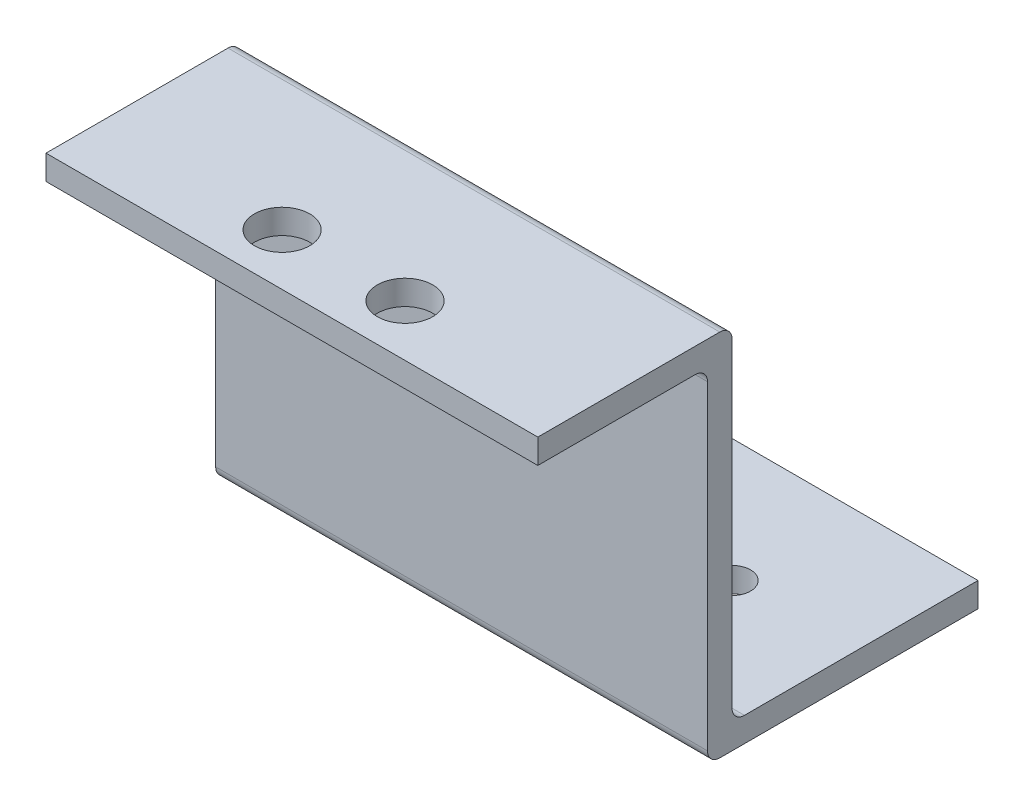
SolidWorks part; units mm, degrees
ref_plane "Front Plane" through (0, 0, 0) normal (0, 0, 1) x (1, 0, 0)
ref_plane "Top Plane" through (0, 0, 0) normal (0, 1, 0) x (1, 0, 0)
ref_plane "Right Plane" through (0, 0, 0) normal (1, 0, 0) x (0, 0, -1)
sketch "Sketch1" plane through (0, 0, 0) normal (0, 1, 0) x (1, 0, 0)
  line L0 (0.736, 26.632) -> (1.236, 26.632)
  line L1 (0.736, 26.632) -> (0.736, 19.832)
  line L2 (0.736, 19.832) -> (1.236, 19.832)
  line L3 (1.236, 26.632) -> (1.236, 19.832)
  line L4 (0.736, 26.632) -> (0.236, 26.632)
  line L5 (0.736, 26.632) -> (0.736, 19.832)
  line L6 (0.736, 19.832) -> (0.236, 19.832)
  line L7 (0.236, 26.632) -> (0.236, 19.832)
  line L8 (0.736, 19.832) -> (10.736, 19.832)
  line L9 (0.736, 19.832) -> (0.736, -20.568)
  line L10 (0.736, -20.568) -> (10.736, -20.568)
  line L11 (10.736, 19.832) -> (10.736, -20.568)
  line L12 (0.736, 19.832) -> (-9.264, 19.832)
  line L13 (0.736, 19.832) -> (0.736, -20.568)
  line L14 (0.736, -20.568) -> (-9.264, -20.568)
  line L15 (-9.264, 19.832) -> (-9.264, -20.568)
  line L16 (0.736, -20.568) -> (1.236, -20.568)
  line L17 (0.736, -20.568) -> (0.736, -27.368)
  line L18 (0.736, -27.368) -> (1.236, -27.368)
  line L19 (1.236, -20.568) -> (1.236, -27.368)
  line L20 (0.736, -20.568) -> (0.236, -20.568)
  line L21 (0.736, -20.568) -> (0.736, -27.368)
  line L22 (0.736, -27.368) -> (0.236, -27.368)
  line L23 (0.236, -20.568) -> (0.236, -27.368)
  line L25 (-19.264, 49.632) -> (20.736, 49.632)
  line L26 (-19.264, 49.632) -> (-19.264, -50.368)
  line L27 (-19.264, -50.368) -> (20.736, -50.368)
  line L28 (20.736, 49.632) -> (20.736, -50.368)
  circle A0 centre (-4.264, 24.032) radius 2.25
  circle A1 centre (5.736, 24.032) radius 2.25
  circle A2 centre (5.736, -24.768) radius 2.25
  circle A3 centre (-4.264, -24.768) radius 2.25
  circle A4 centre (-9.264, 39.632) radius 1.5
  circle A5 centre (10.736, 39.632) radius 1.5
  circle A6 centre (10.736, -40.368) radius 1.5
  circle A7 centre (-9.264, -40.368) radius 1.5
  dimension "D24" = 10
  dimension "D26" = 10
  dimension "D27" = 10
  dimension "D28" = 10
  dimension "D29" = 10
  dimension "D30" = 10
  dimension "D31" = 10
  dimension "D1" = 0.5
  dimension "D2" = 0.5
  dimension "D3" = 6.8
  dimension "D4" = 40.4
  dimension "D5" = 10
  dimension "D6" = 10
  dimension "D7" = 4.5
  dimension "D8" = 4.2
  dimension "D9" = 4.5
  dimension "D10" = 4.2
  dimension "D11" = 0.5
  dimension "D12" = 0.5
  dimension "D13" = 6.8
  dimension "D14" = 4.2
  dimension "D15" = 4.5
  dimension "D16" = 4.5
  dimension "D17" = 4.2
  dimension "D18" = 100
  dimension "D19" = 40
  dimension "D20" = 23
  dimension "D21" = 23
  dimension "D22" = 10
  dimension "D23" = 10
  dimension "D25" = 10
extrude "Boss-Extrude1" add sketch "Sketch1" along normal blind 2 contours L28 L25 L26 L27 A7 A6 A5 A4 A3 A2 A1 A0 L23 L14 L15 L12 L7 L4 L0 L3 L8 L11 L10 L19 L18 L22 region at (0.736, 0, -48.555)
sketch "Sketch2" plane through (0, 2, 0) normal (0, 1, 0) x (1, 0, 0)
  line L0 (20.736, 49.632) -> (20.736, -50.368) construction
  line L1 (-19.264, 49.632) -> (20.736, 49.632)
  line L2 (-19.264, 49.632) -> (-19.264, 33.632)
  line L3 (-19.264, 33.632) -> (20.736, 33.632)
  line L4 (20.736, 49.632) -> (20.736, 33.632)
  line L6 (-19.264, -50.368) -> (20.736, -50.368)
  line L7 (-19.264, -50.368) -> (-19.264, -34.368)
  line L8 (-19.264, -34.368) -> (20.736, -34.368)
  line L9 (20.736, -50.368) -> (20.736, -34.368)
  dimension "D1" = 40
  dimension "D2" = 16
  dimension "D3" = 40
  dimension "D4" = 16
extrude "Cut-Extrude1" cut sketch "Sketch2" against normal blind 10
sketch "Sketch4" plane through (0, 2, 0) normal (0, 1, 0) x (1, 0, 0)
  line L1 (-19.264, -34.368) -> (20.736, -34.368)
  line L2 (-19.264, -34.368) -> (-19.264, -36.368)
  line L3 (-19.264, -36.368) -> (20.736, -36.368)
  line L4 (20.736, -34.368) -> (20.736, -36.368)
  line L5 (20.736, 33.632) -> (-19.264, 33.632)
  line L6 (20.736, 33.632) -> (20.736, 35.632)
  line L7 (20.736, 35.632) -> (-19.264, 35.632)
  line L8 (-19.264, 33.632) -> (-19.264, 35.632)
  dimension "D1" = 2
  dimension "D2" = 40
  dimension "D3" = 40
  dimension "D4" = 2
extrude "Boss-Extrude2" add sketch "Sketch4" against normal blind 30
sketch "Sketch5" plane through (0, 0, -35.632) normal (0, 0, -1) x (-1, 0, 0)
  line L0 (19.264, -28) -> (19.264, 2) construction
  line L1 (-20.736, -28) -> (19.264, -28)
  line L2 (-20.736, -28) -> (-20.736, -26)
  line L3 (-20.736, -26) -> (19.264, -26)
  line L4 (19.264, -28) -> (19.264, -26)
  dimension "D1" = 2
  dimension "D2" = 40
extrude "Boss-Extrude3" add sketch "Sketch5" along normal blind 20
sketch "Sketch6" plane through (0, 0, 36.368) normal (0, 0, 1) x (1, 0, 0)
  line L0 (20.736, -28) -> (20.736, 2) construction
  line L1 (-19.264, -28) -> (20.736, -28)
  line L2 (-19.264, -28) -> (-19.264, -26)
  line L3 (-19.264, -26) -> (20.736, -26)
  line L4 (20.736, -28) -> (20.736, -26)
  dimension "D1" = 40
  dimension "D2" = 2
extrude "Boss-Extrude4" add sketch "Sketch6" along normal blind 20
fillet "Fillet1" radius 1 8 edges at (0.736, -28, -33.632) (0.736, -26, -35.632) (0.736, 2, -35.632) (0.736, 0, -33.632) (0.736, 0, 34.368) (0.736, 2, 36.368) (0.736, -28, 34.368) (0.736, -26, 36.368)
sketch "Sketch7" plane through (0, -26, 0) normal (0, 1, 0) x (1, 0, 0)
  line L0 (20.736, 55.632) -> (20.736, 36.632) construction
  line L1 (-19.264, 55.632) -> (20.736, 55.632) construction
  line L2 (-19.264, 55.632) -> (-19.264, 36.632) construction
  circle A0 centre (-9.264, 45.632) radius 1.5
  circle A1 centre (10.736, 45.632) radius 1.5
  dimension "D1" = 3
  dimension "D2" = 3
  dimension "D3" = 10
  dimension "D4" = 10
  dimension "D5" = 10
  dimension "D6" = 10
extrude "Cut-Extrude2" cut sketch "Sketch7" against normal blind 20
sketch "Sketch8" plane through (0, -26, 0) normal (0, 1, 0) x (1, 0, 0)
  line L0 (20.736, -56.368) -> (20.736, -37.368) construction
  line L1 (20.736, -56.368) -> (-19.264, -56.368) construction
  line L2 (-19.264, -56.368) -> (-19.264, -37.368) construction
  circle A0 centre (10.736, -46.368) radius 1.5
  circle A1 centre (-9.264, -46.368) radius 1.5
  dimension "D1" = 10
  dimension "D2" = 10
  dimension "D3" = 10
  dimension "D4" = 10
extrude "Cut-Extrude3" cut sketch "Sketch8" against normal blind 20
sketch "Sketch9" plane through (0, 2, 0) normal (0, 1, 0) x (1, 0, 0)
  line L1 (10.736, 19.832) -> (36.675, 19.832)
  line L2 (10.736, 19.832) -> (10.736, -106.8663)
  line L3 (10.736, -106.8663) -> (36.675, -106.8663)
  line L4 (36.675, 19.832) -> (36.675, -106.8663)
  line L5 (10.736, 19.832) -> (-32.318, 19.832)
  line L6 (10.736, 19.832) -> (10.736, -99.3118)
  line L7 (10.736, -99.3118) -> (-32.318, -99.3118)
  line L8 (-32.318, 19.832) -> (-32.318, -99.3118)
  line M1 (20.736, -35.368) -> (20.736, 34.632)
  line M3 (-19.264, 34.632) -> (-19.264, -35.368)
  line M4 (-19.264, -35.368) -> (20.736, -35.368)
  circle M5 centre (-4.264, -24.768) radius 2.25
  circle M6 centre (5.736, -24.768) radius 2.25
  line M9 (0.236, -27.368) -> (0.236, -20.568)
  line M10 (0.236, -20.568) -> (-9.264, -20.568)
  line M11 (-9.264, -20.568) -> (-9.264, 19.832)
  line M12 (-9.264, 19.832) -> (0.236, 19.832)
  line M16 (1.236, 19.832) -> (10.736, 19.832)
  line M17 (10.736, 19.832) -> (10.736, -20.568)
  line M18 (10.736, -20.568) -> (1.236, -20.568)
  line M19 (1.236, -20.568) -> (1.236, -27.368)
  line M20 (1.236, -27.368) -> (0.236, -27.368)
extrude "Cut-Extrude4" cut sketch "Sketch9" against normal through all contours L4 L1 L2 L3 M1 M4 | L5 M16 M12 M11 M10 M9 M20 M19 M18 M17 | L5 L2 M11 M3 M4 M18 M19 M20 M9 M10 M6 M5 | L2 L1 M17 M4 M1 | L5 L8 L7 L2 M4 M3 region at (15.736, 2, 7.768) region at (0.736, 2, 0.5649) region at (25.3143, 2, 50.7338) region at (-9.4939, 2, 14.3511) region at (-13.9027, 2, 54.982)
sketch "Sketch10" plane through (0, 2, 0) normal (0, 1, 0) x (1, 0, 0)
  line L1 (0.236, 26.632) -> (1.236, 26.632)
  line L2 (0.236, 26.632) -> (0.236, 19.832)
  line L3 (0.236, 19.832) -> (1.236, 19.832)
  line L4 (1.236, 26.632) -> (1.236, 19.832)
extrude "Boss-Extrude5" add sketch "Sketch10" against normal blind 2
